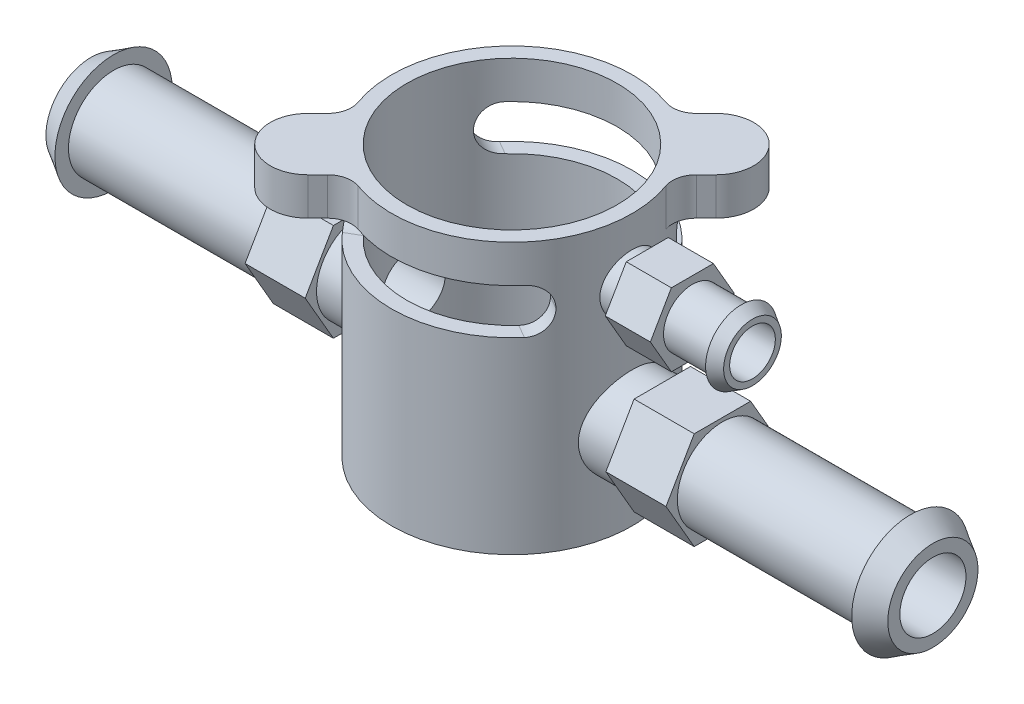
SolidWorks part; units mm, degrees
material "Chrome Stainless Steel"
ref_plane "Front Plane" through (0, 0, 0) normal (0, 0, 1) x (1, 0, 0)
ref_plane "Top Plane" through (0, 0, 0) normal (0, 1, 0) x (1, 0, 0)
ref_plane "Right Plane" through (0, 0, 0) normal (1, 0, 0) x (0, 0, -1)
ref_plane "Plane1" through (0, 0, 0) normal (-0.7071, 0, 0.7071) x (0.7071, 0, 0.7071)
sketch "Sketch1" plane through (0, 0, 0) normal (0, 1, 0) x (1, 0, 0)
  circle A0 centre (0, 0) radius 25.4
extrude "Boss-Extrude1" add sketch "Sketch1" along normal blind 57.15
sketch "Sketch2" plane through (0, 0, 0) normal (1, 0, 0) x (0, 0, -1)
  line L0 (0, 0) -> (0, 58.6228) construction
  line L2 (-5.9575, 29.3687) -> (-11.9151, 19.05)
  line L3 (-11.9151, 19.05) -> (-5.9575, 8.7313)
  line L4 (-5.9575, 8.7313) -> (5.9575, 8.7313)
  line L5 (5.9575, 8.7313) -> (11.9151, 19.05)
  line L6 (11.9151, 19.05) -> (5.9575, 29.3687)
  line L7 (5.9575, 29.3687) -> (-5.9575, 29.3687)
  line L8 (4.4361, 52.1335) -> (-4.4361, 52.1335)
  line L9 (-4.4361, 52.1335) -> (-8.8721, 44.45)
  line L10 (-8.8721, 44.45) -> (-4.4361, 36.7665)
  line L11 (-4.4361, 36.7665) -> (4.4361, 36.7665)
  line L12 (4.4361, 36.7665) -> (8.8721, 44.45)
  line L13 (8.8721, 44.45) -> (4.4361, 52.1335)
  circle A0 centre (0, 19.05) radius 6.985
  circle A1 centre (0, 44.45) radius 4.826
  circle A2 centre (0, 19.05) radius 9.525
  circle A3 centre (0, 44.45) radius 6.096
  circle A4 centre (0, 19.05) radius 10.3187 construction
  circle A5 centre (0, 44.45) radius 7.6835 construction
  dimension "D1" = 13.97
  dimension "D3" = 9.652
  dimension "D7" = 0.7937
  dimension "D8" = 1.5875
  dimension "D4" = 25.4
  dimension "D5" = 19.05
  dimension "D2" = 2.54
  dimension "D6" = 1.27
extrude "Boss-Extrude2" add sketch "Sketch2" along normal blind 88.9 contours A2
extrude "Boss-Extrude3" add sketch "Sketch2<3>" along normal blind 50.8 contours A3
sketch "Sketch2<3>" plane through (0, 0, 0) normal (1, 0, 0) x (0, 0, -1) same geometry as "Sketch2"
sketch "Sketch3" plane through (0, 0, 0) normal (0, 0, 1) x (1, 0, 0)
  line L0 (88.9, 28.575) -> (84.1375, 31.4325)
  line L1 (84.1375, 31.4325) -> (84.1375, 28.575)
  line L2 (88.9, 28.575) -> (25.4, 28.575) construction
  line L3 (84.1375, 28.575) -> (88.9, 28.575)
  dimension "D1" = 4.7625
  dimension "D2" = 2.8575
revolve "Revolve1" add sketch "Sketch3" angle 360 about axis through (88.9, 19.05, 0) along (-1, 0, 0)
sketch "Sketch4" plane through (0, 0, 0) normal (0, 0, 1) x (1, 0, 0)
  line L0 (50.8, 50.546) -> (48.4187, 50.546)
  line L1 (50.8, 50.546) -> (25.4, 50.546) construction
  line L2 (48.4187, 50.546) -> (48.4187, 51.9748)
  line L3 (48.4187, 51.9748) -> (50.8, 50.546)
  dimension "D1" = 2.3813
  dimension "D2" = 1.4287
revolve "Revolve2" add sketch "Sketch4" angle 360 about axis through (50.8, 44.45, 0) along (-1, 0, 0)
extrude "Boss-Extrude5" add sketch "Sketch2<13>" along normal blind 12.7 from offset 31.75 contours L7 L2 L3 L4 L5 L6
sketch "Sketch2<13>" plane through (0, 0, 0) normal (1, 0, 0) x (0, 0, -1) same geometry as "Sketch2"
extrude "Boss-Extrude6" add sketch "Sketch2<14>" along normal blind 9.525 from offset 28.575 contours L9 L10 L11 L12 L13 L8
sketch "Sketch2<14>" plane through (0, 0, 0) normal (1, 0, 0) x (0, 0, -1) same geometry as "Sketch2"
mirror "Mirror2" about plane through (0, 0, 0) normal (1, 0, 0) of "Revolve1", "Boss-Extrude5", "Boss-Extrude2"
sketch "Sketch8" plane through (0, 57.15, 0) normal (0, 1, 0) x (1, 0, 0)
  circle A0 centre (0, 0) radius 25.4 construction
  circle A1 centre (0, 0) radius 25.4 construction
  circle A2 centre (0, 0) radius 22.225
  dimension "D1" = 3.175
extrude "Cut-Extrude2" cut sketch "Sketch8" against normal offset from surface (53.975 mm away) 3.175 up to face at (0, 0, 25.4)
ref_plane "Plane2" through (0, 0, 0) normal (-0.5, 0, 0.866) x (0, -1, 0)
ref_plane "Plane3" through (0, 44.45, 0) normal (0, 1, 0) x (1, 0, 0)
sketch "Sketch7" plane through (0, 44.45, 0) normal (0, 1, 0) x (1, 0, 0)
  line L0 (19.2474, 11.1125) -> (21.997, 12.7)
  line L1 (0, 0) -> (25.4, 0) construction
  line L2 (19.2474, -11.1125) -> (21.997, -12.7)
  line L3 (-19.2474, -11.1125) -> (-21.997, -12.7)
  line L4 (-19.2474, 11.1125) -> (-21.997, 12.7)
  line L5 (0, 0) -> (19.2474, -11.1125) construction
  line L6 (0, 0) -> (-19.2474, -11.1125) construction
  line L7 (0, 0) -> (-19.2474, 11.1125) construction
  line L8 (0, 0) -> (19.2474, 11.1125) construction
  circle A0 centre (0, 0) radius 25.4 construction
  arc A1 (21.997, 12.7) -> (-21.997, 12.7) centre (0, 0) ccw
  arc A2 (21.997, -12.7) -> (25.4, 0) centre (0, 0) ccw construction
  arc A3 (25.4, 0) -> (21.997, 12.7) centre (0, 0) ccw construction
  arc A4 (-21.997, 12.7) -> (-21.997, -12.7) centre (0, 0) ccw construction
  arc A5 (-21.997, -12.7) -> (21.997, -12.7) centre (0, 0) ccw
  arc A7 (-19.2474, -11.1125) -> (19.2474, -11.1125) centre (0, 0) ccw
  arc A8 (-19.2474, 11.1125) -> (-19.2474, -11.1125) centre (0, 0) ccw construction
  arc A9 (19.2474, -11.1125) -> (22.225, 0) centre (0, 0) ccw construction
  arc A10 (19.2474, 11.1125) -> (-19.2474, 11.1125) centre (0, 0) ccw
  arc A11 (22.225, 0) -> (19.2474, 11.1125) centre (0, 0) ccw construction
  circle A12 centre (0, 0) radius 22.225 construction
  dimension "D2" = 22.225
  dimension "D1" = 30
extrude "Cut-Extrude1" cut sketch "Sketch7" against normal mid plane 9.525
fillet "Fillet2" radius 4.7625 8 edges at (20.6222, 49.2125, -11.9063) (20.6222, 39.6875, -11.9063) (-20.6222, 49.2125, -11.9063) (-20.6222, 39.6875, -11.9063) (-20.6222, 49.2125, 11.9063) (-20.6222, 39.6875, 11.9063) (20.6222, 49.2125, 11.9063) (20.6222, 39.6875, 11.9063)
sketch "Sketch5" plane through (0, 57.15, 0) normal (0, 1, 0) x (1, 0, 0)
  line L0 (-21.5526, -21.5526) -> (21.5526, 21.5526) construction
  line L2 (-35.5409, 0) -> (35.5409, 0) construction
  line L3 (11.4483, 22.6737) -> (15.94, 27.1653)
  line L4 (15.94, 27.1653) -> (27.1653, 15.94) construction
  line L5 (27.1653, 15.94) -> (22.6737, 11.4483)
  circle A0 centre (0, 0) radius 25.4 construction
  arc A1 (15.94, 27.1653) -> (27.1653, 15.94) centre (21.5526, 21.5526) cw
  arc A2 (22.6737, 11.4483) -> (11.4483, 22.6737) centre (0, 0) ccw
  point P0 (0, 0)
  point P6 (0, 0)
  dimension "D1" = 45
  dimension "D3" = 15.875
  dimension "D2" = 30.48
extrude "Boss-Extrude4" add sketch "Sketch5" against normal up to surface (7.9375 mm away) contours A1 L5 A2 L3 up to face at (0, 49.2125, -19.8008)
fillet "Fillet1" radius 5.08 2 edges at (11.4483, 53.1812, -22.6737) (22.6737, 53.1812, -11.4483)
mirror "Mirror1" about plane through (0, 0, 0) normal (-0.7071, 0, 0.7071) of "Fillet1", "Boss-Extrude4"
extrude "Cut-Extrude3" cut sketch "Sketch2<10>" against normal through all both and the other way through all contours A0
sketch "Sketch2<10>" plane through (0, 0, 0) normal (1, 0, 0) x (0, 0, -1) same geometry as "Sketch2"
extrude "Cut-Extrude5" cut sketch "Sketch2<12>" along normal through all contours A1
sketch "Sketch2<12>" plane through (0, 0, 0) normal (1, 0, 0) x (0, 0, -1) same geometry as "Sketch2"
equation "\"D19@Boss-Extrude2\"=2"
equation "\"D2@Sketch3\"=\"D1@Sketch3\"*3/5"
equation "\"D2@Sketch4\"=\"D1@Sketch4\"*3/5"
equation "\"D2@Sketch5\"=\"D1@Sketch1\"*3/5"
